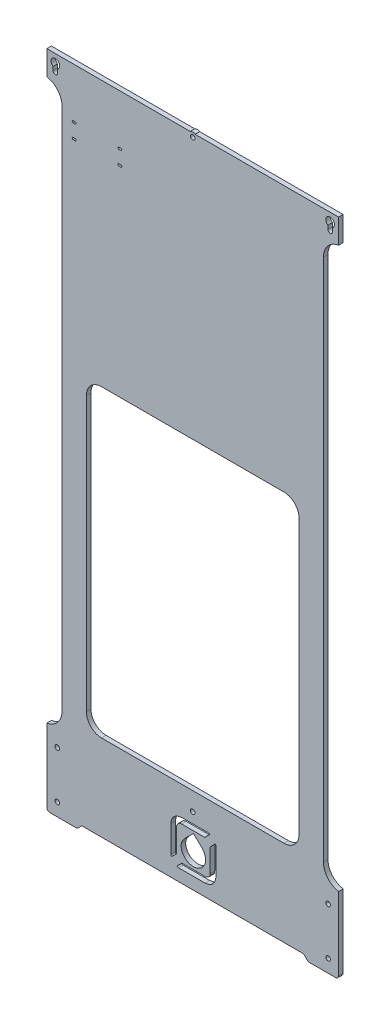
SolidWorks part; units mm, degrees
material "6061-T6 Black anodised"
ref_plane "Front Plane" through (0, 0, 0) normal (0, 0, 1) x (1, 0, 0)
ref_plane "Top Plane" through (0, 0, 0) normal (0, 1, 0) x (1, 0, 0)
ref_plane "Right Plane" through (0, 0, 0) normal (1, 0, 0) x (0, 0, -1)
sketch "Sketch1" plane through (0, 0, 0) normal (0, 0, 1) x (1, 0, 0)
  line L0 (89.02, 0) -> (-89.02, 0) construction
  line L1 (95.92, 394.5) -> (-95.92, 394.5)
  line L2 (95.92, 394.5) -> (95.92, -36.5)
  line L3 (72.92, -36.5) -> (-72.92, -36.5)
  line L4 (-95.92, 394.5) -> (-95.92, -36.5)
  line L5 (95.92, 394.5) -> (-95.92, -36.5) construction
  line L6 (95.92, -36.5) -> (-95.92, 394.5) construction
  line L7 (-90.52, -31) -> (-90.52, -28.5767) construction
  line L8 (-90.32, 384) -> (90.32, 384) construction
  line L9 (0, 384) -> (0, 0) construction
  line L10 (-91.82, 384) -> (-91.82, 386.4233)
  line L11 (-88.82, 384) -> (-88.82, 386.4233)
  line L12 (-90.52, 0) -> (-90.52, 2.4233) construction
  line L13 (-87.52, 0) -> (-87.52, 2.4233) construction
  line L14 (-87.52, -31) -> (-87.52, -28.5767) construction
  line L15 (87.52, -31) -> (87.52, -28.5767) construction
  line L16 (90.52, -31) -> (90.52, -28.5767) construction
  line L17 (87.52, 0) -> (87.52, 2.4233) construction
  line L18 (90.52, 0) -> (90.52, 2.4233) construction
  line L19 (88.82, 384) -> (88.82, 386.4233)
  line L20 (91.82, 384) -> (91.82, 386.4233)
  line L21 (-95.92, -36.5) -> (-95.92, -39.5)
  line L22 (-95.92, -39.5) -> (-75.92, -39.5)
  line L23 (-75.92, -39.5) -> (-72.92, -36.5)
  line L24 (95.92, -36.5) -> (95.92, -39.5)
  line L25 (95.92, -39.5) -> (75.92, -39.5)
  line L26 (75.92, -39.5) -> (72.92, -36.5)
  arc A0 (-90.52, 0) -> (-87.52, 0) centre (-89.02, 0) ccw
  arc A1 (87.52, 0) -> (90.52, 0) centre (89.02, 0) ccw
  arc A2 (-90.52, -31) -> (-87.52, -31) centre (-89.02, -31) ccw
  arc A4 (-91.82, 384) -> (-88.82, 384) centre (-90.32, 384) ccw
  arc A5 (88.82, 384) -> (91.82, 384) centre (90.32, 384) ccw
  arc A6 (-88.82, 386.4233) -> (-91.82, 386.4233) centre (-90.32, 388.8466) ccw
  circle A7 centre (-90.32, 384) radius 2.85 construction
  arc A8 (-87.52, 2.4233) -> (-90.52, 2.4233) centre (-89.02, 4.8466) ccw construction
  circle A9 centre (-89.02, 0) radius 2.85 construction
  arc A10 (-87.52, -28.5767) -> (-90.52, -28.5767) centre (-89.02, -26.1534) ccw construction
  circle A11 centre (-89.02, -31) radius 2.85 construction
  arc A12 (90.52, -28.5767) -> (87.52, -28.5767) centre (89.02, -26.1534) ccw construction
  circle A13 centre (89.02, -31) radius 2.85 construction
  arc A14 (90.52, 2.4233) -> (87.52, 2.4233) centre (89.02, 4.8466) ccw construction
  circle A15 centre (89.02, 0) radius 2.85 construction
  arc A16 (91.82, 386.4233) -> (88.82, 386.4233) centre (90.32, 388.8466) ccw
  circle A17 centre (90.32, 384) radius 2.85 construction
  circle A18 centre (89.02, -31) radius 1.5
  arc A19 (90.52, 0) -> (87.52, 0) centre (89.02, 0) ccw
  arc A20 (-87.52, 0) -> (-90.52, 0) centre (-89.02, 0) ccw
  arc A21 (-87.52, -31) -> (-90.52, -31) centre (-89.02, -31) ccw
  point P0 (0, 179)
  dimension "D4" = 3
  dimension "D7" = 5.6
  dimension "D9" = 5.7
  dimension "D1" = 191.84
  dimension "D2" = 431
  dimension "D3" = 6.9
  dimension "D5" = 31
  dimension "D6" = 5.5
  dimension "D8" = 10.5
  dimension "D10" = 45
  dimension "D11" = 20
  dimension "D12" = 3
extrude "Boss-Extrude1" add sketch "Sketch1" along normal blind 3
sketch "Sketch2" plane through (0, 0, 3) normal (0, 0, 1) x (1, 0, 0)
  line L0 (-95.92, 394.5) -> (-95.92, -39.5) construction
  line L1 (-95.92, 10.5) -> (-85.92, 10.5)
  line L2 (-95.92, 10.5) -> (-95.92, 378.5)
  line L3 (-95.92, 378.5) -> (-85.92, 378.5)
  line L4 (-85.92, 10.5) -> (-85.92, 378.5)
  line L5 (95.92, -39.5) -> (95.92, 394.5) construction
  line L6 (95.92, 10.5) -> (85.92, 10.5)
  line L7 (95.92, 10.5) -> (95.92, 378.5)
  line L8 (95.92, 378.5) -> (85.92, 378.5)
  line L9 (85.92, 10.5) -> (85.92, 378.5)
  line L10 (95.92, 394.5) -> (-95.92, 394.5) construction
  line L11 (-72.92, -36.5) -> (72.92, -36.5) construction
  dimension "D1" = 16
  dimension "D2" = 47
  dimension "D3" = 10
extrude "Cut-Extrude1" cut sketch "Sketch2" against normal through all
fillet "Fillet1" radius 12 4 edges at (85.92, 10.5, 1.5) (-85.92, 10.5, 1.5) (85.92, 378.5, 1.5) (-85.92, 378.5, 1.5)
sketch "Sketch3" plane through (0, 0, 3) normal (0, 0, 1) x (1, 0, 0)
  line L0 (-72.92, -36.5) -> (72.92, -36.5) construction
  line L1 (95.92, 394.5) -> (-95.92, 394.5) construction
  circle A0 centre (0, 8) radius 1.5
  circle A2 centre (0, 392) radius 1.5
  dimension "D2" = 2.5
  dimension "D3" = 3
  dimension "D1" = 44.5
extrude "Cut-Extrude2" cut sketch "Sketch3" against normal through all
sketch "Sketch4" plane through (0, 0, 3) normal (0, 0, 1) x (1, 0, 0)
  line L0 (-85.92, 22.3322) -> (-85.92, 366.6678) construction
  line L1 (-69.92, 220) -> (69.92, 220)
  line L2 (-69.92, 220) -> (-69.92, 20)
  line L3 (-69.92, 20) -> (69.92, 20)
  line L4 (69.92, 220) -> (69.92, 20)
  line L5 (-69.92, 220) -> (69.92, 20) construction
  line L6 (-69.92, 20) -> (69.92, 220) construction
  circle A0 centre (0, 8) radius 1.5 construction
  point P0 (0, 120)
  dimension "D1" = 16
  dimension "D2" = 12
  dimension "D3" = 200
extrude "Cut-Extrude3" cut sketch "Sketch4" against normal through all
fillet "Fillet2" radius 10 4 edges at (69.92, 220, 1.5) (-69.92, 220, 1.5) (69.92, 20, 1.5) (-69.92, 20, 1.5)
sketch "Sketch7" plane through (0, 0, 3) normal (0, 0, 1) x (1, 0, 0)
  line L0 (0, -4.6257) -> (-4.8534, -9.4789)
  line L1 (6.0015, -9.4789) -> (0.8516, -4.6257)
  line L2 (-7.2622, -2.659) -> (7.8165, -2.659)
  line L3 (8.077, -2.549) -> (11.0039, 0.3781)
  line L4 (10.2253, 1.0822) -> (-7.2622, 1.0822)
  line L5 (-14.4113, -6.0673) -> (-14.4098, -23.5545)
  line L6 (-13.7057, -24.3315) -> (-10.7801, -21.4046)
  line L7 (-10.6686, -21.1457) -> (-10.67, -6.0673)
  line L8 (8.1139, -24.8541) -> (-6.9645, -24.8541)
  line L9 (-7.2249, -24.9656) -> (-10.1519, -27.8925)
  line L10 (-9.3733, -28.5967) -> (8.1139, -28.5967)
  line L11 (15.2633, -21.4459) -> (15.2619, -3.9601)
  line L12 (14.5577, -3.1829) -> (11.6308, -6.1099)
  line L13 (11.5207, -6.3688) -> (11.5218, -21.4459)
  spline S0 degree 3 poles (0.4439, -4.4409) (0.3912, -4.446) (0.2828, -4.4565) (0.1286, -4.5203) (0.0426, -4.5908) (0, -4.6257) knots 0 0 0 0 0.322338 0.663828 1 1 1 1
  spline S1 degree 3 poles (-4.8534, -9.4789) (-4.8579, -9.4831) (-4.8667, -9.4912) (-4.8791, -9.5037) (-5.3375, -10.01) (-6.231, -11.0554) (-7.3312, -12.8598) (-7.8887, -15.6825) (-6.8483, -19.2199) (-3.8783, -22.1689) (0.2577, -23.4427) (4.5569, -22.3845) (7.7118, -19.2149) (8.7217, -15.6934) (8.2109, -12.8985) (7.2971, -11.0248) (6.4234, -9.9823) (6.0015, -9.4789) knots 0 0 0 0 0.000489 0.000958 0.001407 0.055151 0.111018 0.168413 0.280621 0.389777 0.490762 0.614387 0.723194 0.83533 0.891393 0.947551 1 1 1 1
  spline S2 degree 3 poles (0.8516, -4.6257) (0.8125, -4.5919) (0.7352, -4.5249) (0.5954, -4.4557) (0.4944, -4.4458) (0.4439, -4.4409) knots 0 0 0 0 0.338885 0.669777 1 1 1 1
  spline S3 degree 3 poles (7.8165, -2.659) (7.8386, -2.6573) (7.882, -2.6541) (7.9472, -2.6464) (7.9964, -2.6204) (8.0324, -2.5949) (8.0557, -2.5715) (8.07, -2.5564) (8.077, -2.549) knots 0 0 0 0 0.227493 0.445972 0.663373 0.787115 0.896006 1 1 1 1
  spline S4 degree 3 poles (11.0039, 0.3781) (11.0329, 0.4173) (11.0909, 0.496) (11.1149, 0.6442) (11.0877, 0.7801) (11.0204, 0.8896) (10.9299, 0.9685) (10.7969, 1.0179) (10.6368, 1.0502) (10.4517, 1.0835) (10.3213, 1.081) (10.25, 1.0825) (10.2377, 1.0831) (10.2294, 1.0825) (10.2253, 1.0822) knots 0 0 0 0 0.104345 0.208931 0.313565 0.397995 0.482811 0.567894 0.701187 0.836715 0.973247 0.982163 0.991064 1 1 1 1
  spline S5 degree 3 poles (-7.2622, 1.0822) (-8.5111, 0.8827) (-10.9772, 0.4887) (-13.8177, -2.3518) (-14.2117, -4.8181) (-14.4113, -6.0673) knots 0 0 0 0 0.336154 0.663772 1 1 1 1
  spline S6 degree 3 poles (-14.4098, -23.5545) (-14.4101, -23.5584) (-14.4107, -23.5663) (-14.4101, -23.5782) (-14.4085, -23.6494) (-14.4116, -23.78) (-14.3778, -23.9655) (-14.348, -24.1263) (-14.2965, -24.2584) (-14.2178, -24.3487) (-14.1086, -24.4167) (-13.9724, -24.4439) (-13.8239, -24.4196) (-13.7451, -24.3609) (-13.7057, -24.3315) knots 0 0 0 0 0.008622 0.017031 0.025643 0.162638 0.298245 0.431901 0.516392 0.601007 0.685957 0.790142 0.895037 1 1 1 1
  spline S7 degree 3 poles (-10.7801, -21.4046) (-10.7711, -21.3953) (-10.7536, -21.3772) (-10.7264, -21.3501) (-10.6977, -21.3146) (-10.6778, -21.2655) (-10.6682, -21.2062) (-10.6685, -21.1664) (-10.6686, -21.1457) knots 0 0 0 0 0.131285 0.25763 0.390972 0.594165 0.788898 1 1 1 1
  spline S8 degree 3 poles (-10.67, -6.0673) (-10.5818, -5.4634) (-10.4093, -4.283) (-9.0474, -2.92) (-7.8666, -2.7474) (-7.2622, -2.659) knots 0 0 0 0 0.33841 0.661392 1 1 1 1
  spline S9 degree 3 poles (-6.9645, -24.8541) (-6.9836, -24.8548) (-7.0187, -24.8562) (-7.0727, -24.8646) (-7.117, -24.885) (-7.157, -24.9087) (-7.1915, -24.9347) (-7.2134, -24.955) (-7.2249, -24.9656) knots 0 0 0 0 0.196746 0.361608 0.557262 0.692766 0.839563 1 1 1 1
  spline S10 degree 3 poles (-10.1519, -27.8925) (-10.1809, -27.9318) (-10.2389, -28.0105) (-10.2629, -28.1587) (-10.2357, -28.2947) (-10.1681, -28.4041) (-10.0777, -28.4828) (-9.9452, -28.5327) (-9.7851, -28.5653) (-9.6, -28.5955) (-9.4695, -28.601) (-9.3981, -28.5958) (-9.3857, -28.5965) (-9.3774, -28.5966) (-9.3733, -28.5967) knots 0 0 0 0 0.104385 0.20895 0.313569 0.398093 0.483012 0.567612 0.700915 0.836485 0.973043 0.982112 0.991066 1 1 1 1
  spline S11 degree 3 poles (8.1139, -28.5967) (9.3629, -28.3971) (11.8293, -28.0028) (14.6704, -25.162) (15.064, -22.6952) (15.2633, -21.4459) knots 0 0 0 0 0.336157 0.663806 1 1 1 1
  spline S12 degree 3 poles (15.2619, -3.9601) (15.2622, -3.956) (15.2628, -3.9477) (15.2621, -3.9352) (15.2606, -3.8638) (15.2632, -3.7334) (15.2298, -3.5483) (15.198, -3.3882) (15.148, -3.2557) (15.0694, -3.1653) (14.9599, -3.0977) (14.8239, -3.0705) (14.6754, -3.0949) (14.597, -3.1536) (14.5577, -3.1829) knots 0 0 0 0 0.008953 0.017947 0.027021 0.163491 0.298949 0.432165 0.516776 0.601601 0.686035 0.790672 0.895263 1 1 1 1
  spline S13 degree 3 poles (11.6308, -6.1099) (11.6212, -6.1191) (11.6023, -6.1372) (11.5737, -6.165) (11.5433, -6.1982) (11.5265, -6.2477) (11.5219, -6.3062) (11.5211, -6.3471) (11.5207, -6.3688) knots 0 0 0 0 0.134582 0.264928 0.404991 0.586048 0.77989 1 1 1 1
  spline S14 degree 3 poles (11.5218, -21.4459) (11.4339, -22.05) (11.262, -23.2307) (9.8992, -24.5934) (8.7183, -24.7658) (8.1139, -24.8541) knots 0 0 0 0 0.338406 0.661372 1 1 1 1
extrude "Cut-Extrude6" cut sketch "Sketch7" against normal through all
sketch "Sketch8" plane through (0, 0, 3) normal (0, 0, 1) x (1, 0, 0)
  line L0 (95.92, 394.5) -> (-95.92, 394.5) construction
  line L1 (-1.6583, 394.5) -> (1.6583, 394.5)
  arc A0 (1.6583, 394.5) -> (-1.6583, 394.5) centre (0, 392) ccw
  dimension "D1" = 3
extrude "Boss-Extrude2" add sketch "Sketch8" against normal up to surface (3 mm away) up to face at (5.0456, -18.6663, 0)
sketch "Sketch9" plane through (0, 0, 3) normal (0, 0, 1) x (1, 0, 0)
  line L0 (-1.6583, 394.5) -> (-95.92, 394.5) construction
  line L1 (-85.92, 22.3322) -> (-85.92, 366.6678) construction
  line L2 (-78.57, 361.5) -> (-77.27, 361.5) construction
  line L3 (-78.57, 362.15) -> (-77.27, 362.15)
  line L4 (-78.57, 360.85) -> (-77.27, 360.85)
  line L5 (-78.57, 352) -> (-77.27, 352) construction
  line L6 (-78.57, 352.65) -> (-77.27, 352.65)
  line L7 (-78.57, 351.35) -> (-77.27, 351.35)
  line L8 (-48.57, 361.5) -> (-47.27, 361.5) construction
  line L9 (-48.57, 362.15) -> (-47.27, 362.15)
  line L10 (-48.57, 360.85) -> (-47.27, 360.85)
  line L11 (-48.57, 352) -> (-47.27, 352) construction
  line L12 (-48.57, 352.65) -> (-47.27, 352.65)
  line L13 (-48.57, 351.35) -> (-47.27, 351.35)
  line L14 (-78.57, 352) -> (-48.57, 352) construction
  line L15 (-47.92, 361.5) -> (-77.92, 352) construction
  circle A0 centre (-77.92, 361.5) radius 0.65 construction
  circle A1 centre (-77.92, 352) radius 0.65 construction
  arc A2 (-78.57, 362.15) -> (-78.57, 360.85) centre (-78.57, 361.5) ccw
  arc A3 (-77.27, 360.85) -> (-77.27, 362.15) centre (-77.27, 361.5) ccw
  arc A4 (-78.57, 352.65) -> (-78.57, 351.35) centre (-78.57, 352) ccw
  arc A5 (-77.27, 351.35) -> (-77.27, 352.65) centre (-77.27, 352) ccw
  arc A6 (-48.57, 362.15) -> (-48.57, 360.85) centre (-48.57, 361.5) ccw
  arc A7 (-47.27, 360.85) -> (-47.27, 362.15) centre (-47.27, 361.5) ccw
  arc A8 (-48.57, 352.65) -> (-48.57, 351.35) centre (-48.57, 352) ccw
  arc A9 (-47.27, 351.35) -> (-47.27, 352.65) centre (-47.27, 352) ccw
  point P10 (-77.92, 361.5)
  point P15 (-77.92, 352)
  point P25 (-47.92, 361.5)
  point P30 (-47.92, 352)
  dimension "D1" = 1.3
  dimension "D3" = 33
  dimension "D4" = 8
  dimension "D2" = 9.5
  dimension "D6" = 30
  dimension "D5" = 2
extrude "Cut-Extrude7" cut sketch "Sketch9" against normal through all
fillet "Fillet3" radius 2 6 edges at (72.92, -36.5, 1.5) (75.92, -39.5, 1.5) (95.92, -39.5, 1.5) (-72.92, -36.5, 1.5) (-75.92, -39.5, 1.5) (-95.92, -39.5, 1.5)
sketch "Sketch10" plane through (0, 0, 3) normal (0, 0, 1) x (1, 0, 0)
  line L0 (-95.92, 10.5) -> (-95.92, -37.5) construction
  line L1 (-88.02, 7.7) -> (-81.17, 7.7)
  line L2 (-88.02, 7.7) -> (-88.02, -3.5)
  line L3 (-88.02, -3.5) -> (-81.17, -3.5)
  line L4 (-81.17, 7.7) -> (-81.17, -3.5)
  line L5 (-88.02, -23.3) -> (-88.02, -34.5)
  line L6 (-88.02, -34.5) -> (-81.17, -34.5)
  line L7 (-81.17, -23.3) -> (-81.17, -34.5)
  line L8 (-88.02, -23.3) -> (-81.17, -23.3)
  circle A0 centre (0, 8) radius 1.5 construction
  point P4 (-81.17, 0)
  dimension "D5" = 8
  dimension "D1" = 6.85
  dimension "D2" = 11.2
  dimension "D3" = 7.9
  dimension "D4" = 3.5
  dimension "D6" = 2
extrude "Cut-Extrude8" [suppressed] cut sketch "Sketch10" against normal through all
chamfer "Chamfer1" [suppressed] distance 3 angle 10
chamfer "Chamfer2" [suppressed] distance 2 angle 45
mirror "Mirror1" [suppressed] about plane through (0, 0, 0) normal (1, 0, 0)
